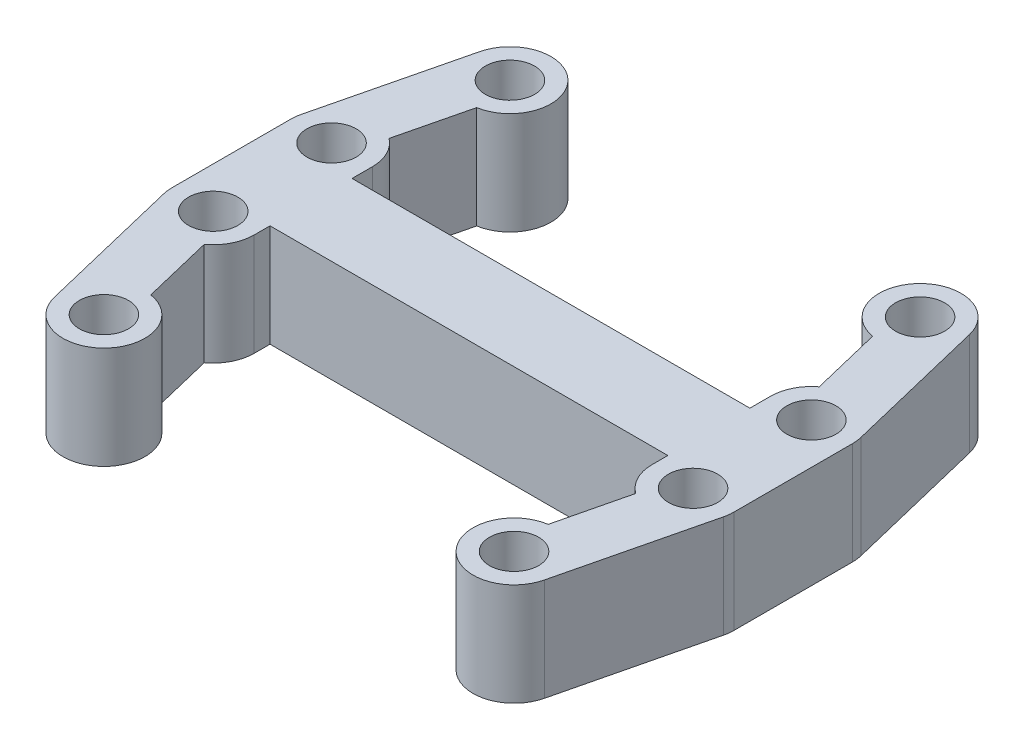
SolidWorks part; units mm, degrees
ref_plane "Front Plane" through (0, 0, 0) normal (0, 0, 1) x (1, 0, 0)
ref_plane "Top Plane" through (0, 0, 0) normal (0, 1, 0) x (1, 0, 0)
ref_plane "Right Plane" through (0, 0, 0) normal (1, 0, 0) x (0, 0, -1)
sketch "Sketch2" plane through (0, 0, 0) normal (0, 1, 0) x (1, 0, 0)
  line L1 (-16.6529, 7.2905) -> (-15.3276, 12.7475)
  line L2 (-18.9603, 16.6243) -> (-21.6591, 5.5118)
  line L3 (-21.7487, 4.7625) -> (-21.7488, -4.3974)
  line L8 (-16.7028, -6.9626) -> (-15.3829, -12.4209)
  line L26 (-18.9611, -16.3038) -> (-21.6598, -5.1436)
  line L29 (0, 10.8515) -> (0, -11.8971) construction
  line L30 (16.6529, 7.2905) -> (15.3276, 12.7475)
  line L31 (18.9603, 16.6243) -> (21.6591, 5.5118)
  line L32 (21.7487, 4.7625) -> (21.7488, -4.3974)
  line L33 (18.9611, -16.3038) -> (21.6598, -5.1436)
  line L34 (16.7028, -6.9626) -> (15.3829, -12.4209)
  line L35 (-15.3988, 4.7625) -> (-15.3988, 3.175)
  line L36 (-15.3988, 3.175) -> (15.3988, 3.175)
  line L37 (-15.3987, -4.3974) -> (-15.3988, -3.175)
  line L38 (-15.3988, -3.175) -> (15.3988, -3.175)
  line L39 (0, 3.175) -> (0, 0) construction
  line L40 (0, 0) -> (0, -3.175) construction
  line L41 (15.3987, -4.3974) -> (15.3988, -3.175)
  line L42 (15.3988, 4.7625) -> (15.3988, 3.175)
  circle A0 centre (-15.875, 15.875) radius 1.905
  arc A1 (-15.3276, 12.7475) -> (-18.9603, 16.6243) centre (-15.875, 15.875) ccw
  circle A2 centre (-18.5738, 4.7625) radius 1.905
  circle A5 centre (-18.5738, -4.3974) radius 1.905
  circle A8 centre (-15.875, -15.5575) radius 1.905
  arc A9 (-15.3988, 4.7625) -> (-16.6529, 7.2905) centre (-18.5738, 4.7625) ccw
  arc A10 (-15.3987, -4.3974) -> (-16.7028, -6.9626) centre (-18.5738, -4.3974) cw
  arc A11 (-15.3829, -12.4209) -> (-18.9611, -16.3038) centre (-15.875, -15.5575) cw
  arc A16 (-21.6591, 5.5118) -> (-21.7487, 4.7625) centre (-18.5738, 4.7625) ccw
  arc A17 (-21.7488, -4.3974) -> (-21.6598, -5.1436) centre (-18.5738, -4.3974) ccw
  arc A18 (15.3988, 4.7625) -> (16.6529, 7.2905) centre (18.5738, 4.7625) cw
  arc A19 (15.3276, 12.7475) -> (18.9603, 16.6243) centre (15.875, 15.875) cw
  arc A20 (21.6591, 5.5118) -> (21.7487, 4.7625) centre (18.5738, 4.7625) cw
  arc A21 (21.7488, -4.3974) -> (21.6598, -5.1436) centre (18.5738, -4.3974) cw
  arc A22 (15.3987, -4.3974) -> (16.7028, -6.9626) centre (18.5738, -4.3974) ccw
  arc A23 (15.3829, -12.4209) -> (18.9611, -16.3038) centre (15.875, -15.5575) ccw
  circle A24 centre (15.875, -15.5575) radius 1.905
  circle A25 centre (18.5738, -4.3974) radius 1.905
  circle A26 centre (18.5738, 4.7625) radius 1.905
  circle A27 centre (15.875, 15.875) radius 1.905
  point P37 (0, -4.3974)
  dimension "D1" = 3.81
  dimension "D2" = 3.175
  dimension "D3" = 3.175
  dimension "D4" = 15.875
  dimension "D5" = 15.875
  dimension "D6" = 15.5575
  dimension "D7" = 4.7625
  dimension "D8" = 18.5738
  dimension "D9" = 4.3974
  dimension "D10" = 4.445
  dimension "D11" = 6.35
extrude "Boss-Extrude1" add sketch "Sketch2" along normal blind 7.9375
